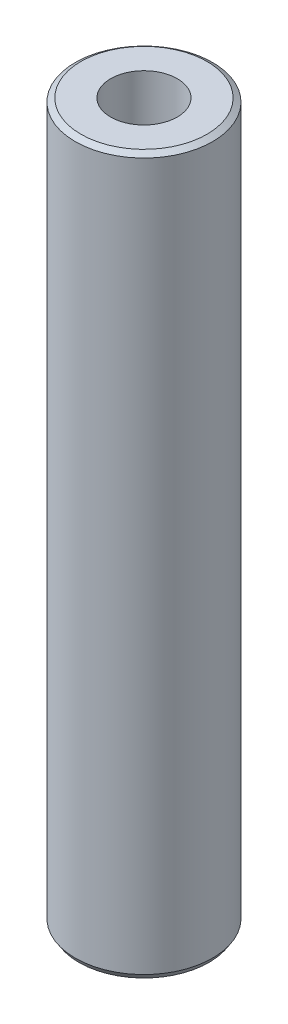
SolidWorks part; units mm, degrees
ref_plane "Front Plane" through (0, 0, 0) normal (0, 0, 1) x (1, 0, 0)
ref_plane "Top Plane" through (0, 0, 0) normal (0, 1, 0) x (1, 0, 0)
ref_plane "Right Plane" through (0, 0, 0) normal (1, 0, 0) x (0, 0, -1)
sketch "Sketch1" plane through (0, 0, 0) normal (0, 1, 0) x (1, 0, 0)
  circle A0 centre (0, 0) radius 57.5
  dimension "SHAFT_OD" = 115
extrude "Boss-Extrude1" add sketch "Sketch1" along normal blind 600
sketch "Sketch2" plane through (0, 0, 0) normal (0, 1, 0) x (1, 0, 0)
  circle A0 centre (0, 0) radius 27.8909
  dimension "BORE_D" = 55.7818
extrude "Cut-Extrude1" cut sketch "Sketch2" along normal through all
chamfer "Chamfer1" distance 3.034 angle 56.98 2 edges at (0, 600, 57.5) (0, 0, 57.5) first distance on face at (0, 600, 57.5) first distance on face at (0, 0, 27.8909)
